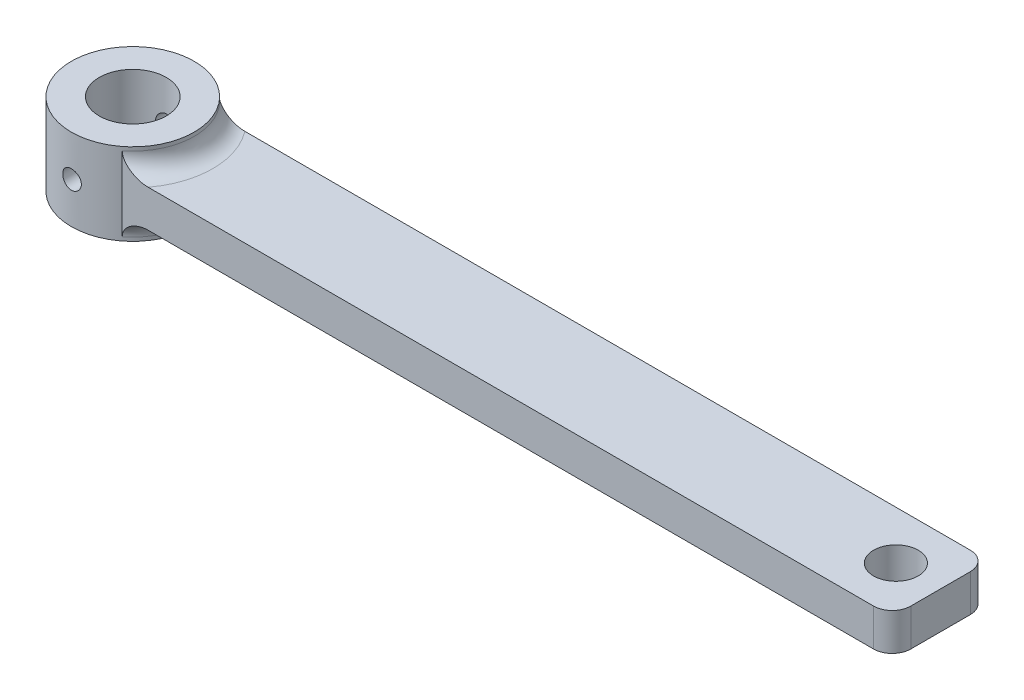
SolidWorks part; units mm, degrees
material "1.0044 (S275JR)"
ref_plane "Płaszczyzna przednia" through (0, 0, 0) normal (0, 0, 1) x (1, 0, 0)
ref_plane "Płaszczyzna górna" through (0, 0, 0) normal (0, 1, 0) x (1, 0, 0)
ref_plane "Płaszczyzna prawa" through (0, 0, 0) normal (1, 0, 0) x (0, 0, -1)
sketch "Szkic1" plane through (0, 0, 0) normal (0, 1, 0) x (1, 0, 0)
  line L1 (0, 0) -> (212, 0)
  line L2 (0, 0) -> (0, 26)
  line L3 (0, 26) -> (212, 26)
  line L4 (217, 5) -> (217, 21)
  arc A0 (212, 0) -> (217, 5) centre (212, 5) ccw
  arc A1 (212, 26) -> (217, 21) centre (212, 21) cw
  circle A2 centre (205, 13) radius 6
  point P7 (217, 0)
  point P10 (217, 26)
  dimension "D3" = 5
  dimension "D4" = 12
  dimension "D1" = 217
  dimension "D2" = 26
  dimension "D5" = 13
  dimension "D6" = 12
extrude "Dodanie-wyciągnięcie1" add sketch "Szkic1" along normal blind 10
sketch "Szkic2" plane through (0, 10, 0) normal (0, 1, 0) x (1, 0, 0)
  line L0 (0, 26) -> (0, 0) construction
  circle A0 centre (0, 13) radius 16.5
  dimension "D1" = 33
extrude "Dodanie-wyciągnięcie2" add sketch "Szkic2" along normal blind 6 and the other way blind 16
sketch "Szkic3" plane through (0, 16, 0) normal (0, 1, 0) x (1, 0, 0)
  circle A0 centre (0, 13) radius 9
  dimension "D1" = 18
extrude "Wytnij-wyciągnięcie1" cut sketch "Szkic3" against normal through all
sketch "Szkic4" plane through (0, 0, 0) normal (0, 0, 1) x (1, 0, 0)
  line L0 (16.5, 16) -> (-16.5, 16) construction
  circle A0 centre (0, 5) radius 2.5
  dimension "D1" = 5
  dimension "D2" = 11
extrude "Wytnij-wyciągnięcie2" cut sketch "Szkic4" against normal through all and the other way through all
fillet "Zaokrąglenie1" radius 5 2 edges at (16.5, 0, -13) (16.5, 10, -13)
